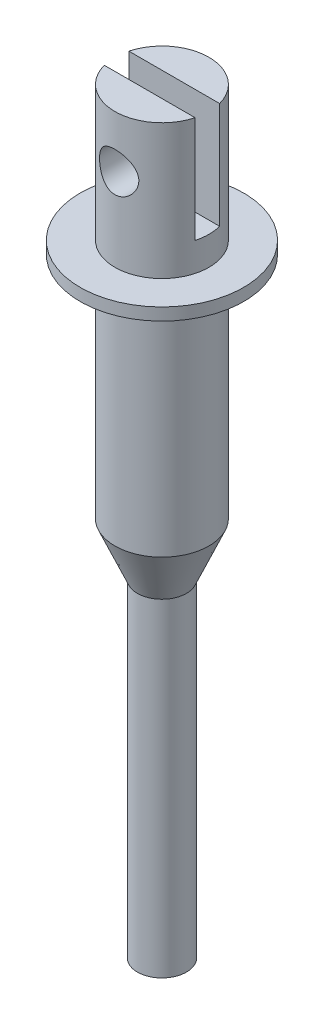
SolidWorks part; units mm, degrees
ref_plane "Front Plane" through (0, 0, 0) normal (0, 0, 1) x (1, 0, 0)
ref_plane "Top Plane" through (0, 0, 0) normal (0, 1, 0) x (1, 0, 0)
ref_plane "Right Plane" through (0, 0, 0) normal (1, 0, 0) x (0, 0, -1)
sketch "Sketch1" plane through (0, 0, 0) normal (0, 0, 1) x (1, 0, 0)
  line L0 (0, 0) -> (1.5, 0)
  line L1 (1.5, 0) -> (1.5, 20.05)
  line L2 (1.5, 20.05) -> (2.875, 23.25)
  line L3 (2.875, 23.25) -> (2.875, 46.25)
  line L4 (2.875, 46.25) -> (0, 46.25)
  line L5 (0, 46.25) -> (0, 0)
  dimension "D1" = 23
  dimension "D2" = 2.875
  dimension "D3" = 1.5
  dimension "D4" = 46.25
  dimension "D5" = 26.2
revolve "Revolve1" add sketch "Sketch1" angle 360 about L5
sketch "Sketch2" plane through (0, 0, 0) normal (0, 0, 1) x (1, 0, 0)
  line L0 (2.875, 46.25) -> (-2.875, 46.25) construction
  line L1 (0, 46.25) -> (0, 44.25) construction
  circle A0 centre (0, 43.05) radius 1.2
  point P2 (0, 44.25)
  dimension "D1" = 2.4
  dimension "D2" = 2
extrude "Cut-Extrude1" cut sketch "Sketch2" against normal through all both and the other way through all
sketch "Sketch3" plane through (0, 46.25, 0) normal (0, 1, 0) x (1, 0, 0)
  line L0 (0, 0) -> (-2.875, 0) construction
  line L5 (-2.875, 0.75) -> (2.875, 0.75)
  line L6 (-2.875, 0.75) -> (-2.875, -0.75)
  line L7 (-2.875, -0.75) -> (2.875, -0.75)
  line L8 (2.875, 0.75) -> (2.875, -0.75)
  circle A1 centre (0, 0) radius 2.875 construction
  dimension "D1" = 1.5
extrude "Cut-Extrude2" cut sketch "Sketch3" against normal blind 6.5
ref_plane "Plane1" through (0, 37.25, 0) normal (0, 1, 0) x (1, 0, 0)
sketch "Sketch4" plane through (0, 37.25, 0) normal (0, 1, 0) x (1, 0, 0)
  circle A0 centre (0, 0) radius 5
  dimension "D1" = 10
extrude "Boss-Extrude1" add sketch "Sketch4" along normal blind 0.75
